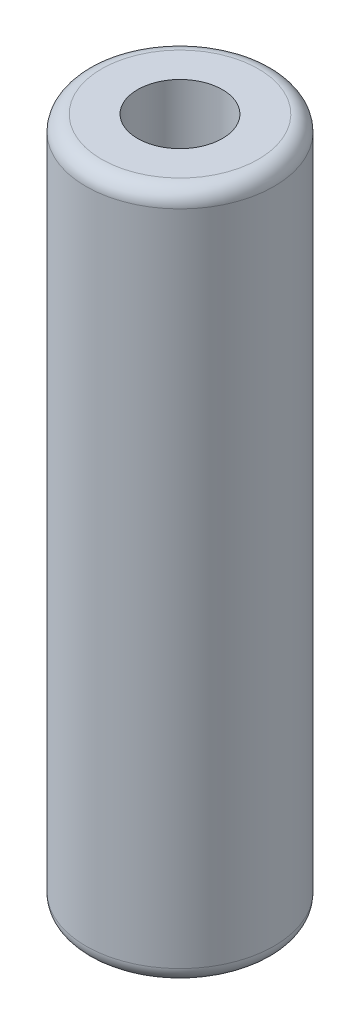
SolidWorks part; units mm, degrees
material "1060 Alloy"
ref_plane "Front Plane" through (0, 0, 0) normal (0, 0, 1) x (1, 0, 0)
ref_plane "Top Plane" through (0, 0, 0) normal (0, 1, 0) x (1, 0, 0)
ref_plane "Right Plane" through (0, 0, 0) normal (1, 0, 0) x (0, 0, -1)
sketch "Sketch1" plane through (0, 0, 0) normal (0, 1, 0) x (1, 0, 0)
  circle A0 centre (0, 0) radius 3
  dimension "D1" = 6
extrude "Boss-Extrude1" add sketch "Sketch1" along normal blind 10.99 and the other way blind 10.99
hole_wizard "#6-32 Tapped Hole1" positions "Sketch2" profile "Sketch3" tap size "#6-32" standard "ANSI Inch"
sketch "Sketch2" plane through (0, 10.99, 0) normal (0, 1, 0) x (1, 0, 0)
  point P0 (0, 0)
sketch "Sketch3" plane through (0, 10.99, 0) normal (1, 0, 0) x (0, 0, 1)
  line L0 (0, 0) -> (0, 8.8127)
  line L1 (0, 8.8127) -> (1.3525, 8)
  line L2 (1.3525, 8) -> (1.3525, 0)
  line L5 (1.3525, 0) -> (0, 0)
  line L10 (0, 8.8127) -> (-1.3526, 8) construction
  line L11 (0, -6.35) -> (0, 107.95) construction
  dimension "Tap Drill Dia." = 2.7051
  dimension "Tap Drill Depth" = 8
  dimension "Drill Angle" = 118
fillet "Fillet1" radius 0.5 2 edges at (0, -10.99, 3) (0, 10.99, 3)
mirror "Mirror1" about plane through (0, 0, 0) normal (0, 1, 0) of "#6-32 Tapped Hole1"
